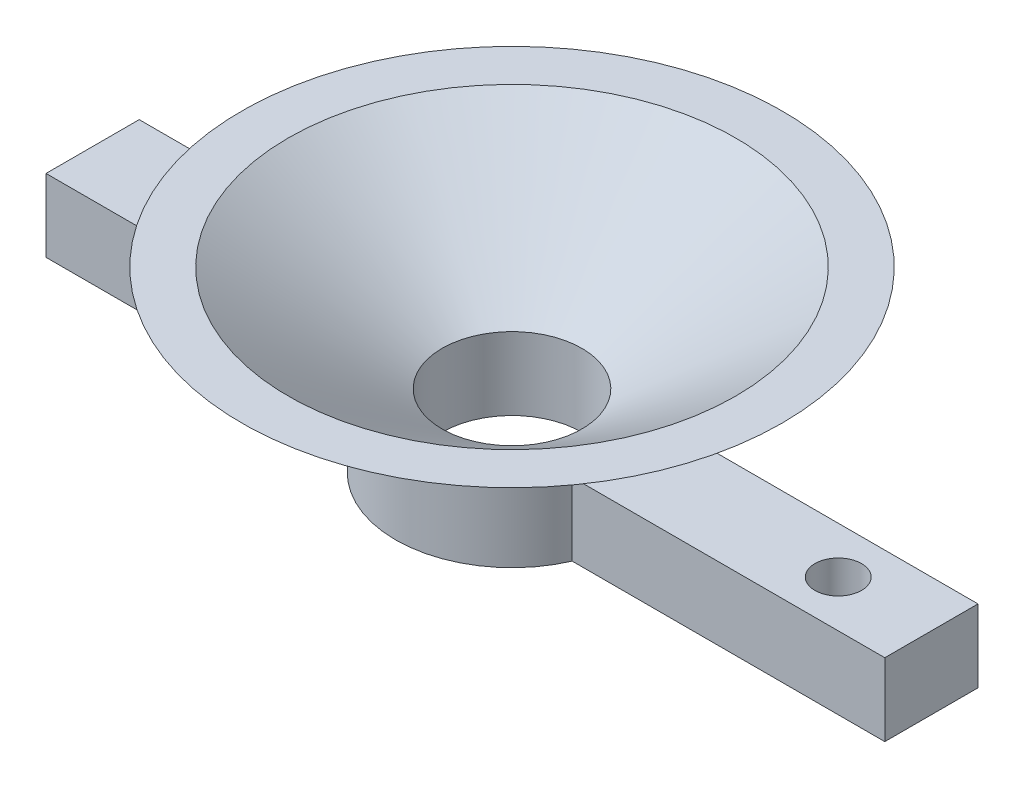
SolidWorks part; units mm, degrees
ref_plane "Front Plane" through (0, 0, 0) normal (0, 0, 1) x (1, 0, 0)
ref_plane "Top Plane" through (0, 0, 0) normal (0, 1, 0) x (1, 0, 0)
ref_plane "Right Plane" through (0, 0, 0) normal (1, 0, 0) x (0, 0, -1)
sketch "Sketch1" plane through (0, 0, 0) normal (0, 1, 0) x (1, 0, 0)
  line L0 (0, -1000) -> (0, 49000) construction
  line L5 (-14.2875, -1.5875) -> (14.2875, -1.5875)
  line L6 (-14.2875, -1.5875) -> (-14.2875, 1.5875)
  line L7 (-14.2875, 1.5875) -> (14.2875, 1.5875)
  line L8 (14.2875, -1.5875) -> (14.2875, 1.5875)
  circle A4 centre (0, 0) radius 2.3813
  circle A5 centre (0, 0) radius 3.9688
  circle A6 centre (-11.1125, 0) radius 0.7937
  circle A7 centre (11.1125, 0) radius 0.7937
  point P4 (0, 1.5875)
  point P6 (-14.2875, 0)
  dimension "D3" = 1.5875
  dimension "D4" = 7.9375
  dimension "D6" = 11.1125
  dimension "D5" = 1.5875
  dimension "D1" = 3.175
  dimension "D2" = 28.575
extrude "Boss-Extrude1" add sketch "Sketch1" along normal mid plane 2.4765 contours L8 | L8 | L5 A5 L7 A4 | L7 A5 L5 A4 | A5 L7 L6 L5 | A5 L5 L8 L7 | L7 A5 A4 | A5 | A4 region at (-8.9437, 0, 0) region at (-3.019, 0, 0) region at (0, 0, -2.6919) region at (8.9437, 0, 0) region at (3.019, 0, 0)
sketch "Sketch2" plane through (0, 0, 0) normal (0, 0, 1) x (1, 0, 0)
  line L3 (3.6374, 1.2383) -> (-3.6374, 1.2383) construction
  line L4 (0, -1000) -> (0, 49000) construction
  line L5 (-2.3813, 1.2383) -> (-7.62, 4.8268)
  line L9 (-2.3813, 1.2383) -> (-3.9688, 1.2383)
  line L10 (-7.62, 4.8268) -> (-9.2075, 4.8268)
  line L11 (-3.9688, 1.2383) -> (-9.2075, 4.8268)
  point P0 (-2.909, 1.2383)
  dimension "D1" = 6.35
  dimension "D2" = 1.5875
  dimension "D3" = 7.62
revolve "Revolve2" add sketch "Sketch2" angle 360 about L4
